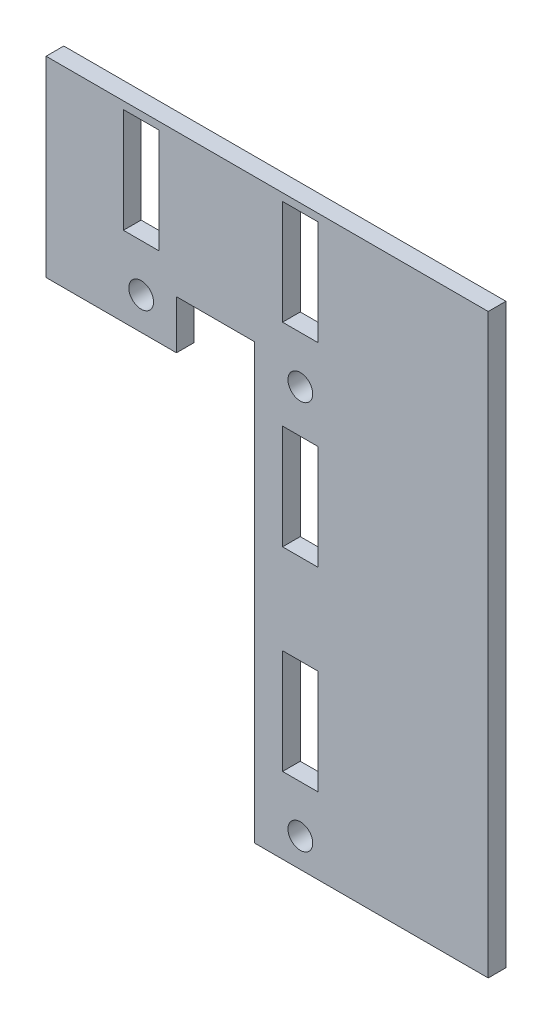
SolidWorks part; units mm, degrees
ref_plane "Front Plane" through (0, 0, 0) normal (1, 0, 0) x (0, 1, 0)
ref_plane "Top Plane" through (0, 0, 0) normal (0, 0, 1) x (0, 1, 0)
ref_plane "Right Plane" through (0, 0, 0) normal (0, 1, 0) x (-1, 0, 0)
sketch "Sketch1" plane through (0, 0, 0) normal (0, 0, 1) x (0, 1, 0)
  line L1 (-50.8, 25.4) -> (50.8, 25.4)
  line L2 (-50.8, 25.4) -> (-50.8, -25.4)
  line L3 (-50.8, -25.4) -> (50.8, -25.4)
  line L4 (50.8, 25.4) -> (50.8, -25.4)
  line L5 (-50.8, 25.4) -> (50.8, -25.4) construction
  line L6 (-50.8, -25.4) -> (50.8, 25.4) construction
  point P0 (0, 0)
  dimension "D1" = 101.6
  dimension "D2" = 50.8
extrude "Boss-Extrude1" add sketch "Sketch1" along normal blind 2.54
sketch "Sketch2" plane through (0, 0, 2.54) normal (0, 0, 1) x (1, 0, 0)
  line L0 (11.1159, -27.94) -> (11.1159, 27.94) construction
  line L1 (11.1159, 27.94) -> (-11.7441, 27.94) construction
  line L2 (-11.7441, 27.94) -> (-11.7441, -27.94) construction
  line L3 (-11.7441, -27.94) -> (11.1159, -27.94) construction
  line L4 (25.4, 50.8) -> (-25.4, 50.8) construction
  circle A0 centre (11.1159, 27.94) radius 1.778
  circle A1 centre (11.1159, -27.94) radius 1.778
  circle A2 centre (-11.7441, 27.94) radius 1.778
  dimension "D3" = 3.556
  dimension "D1" = 55.88
  dimension "D2" = 22.86
  dimension "D4" = 22.86
extrude "Cut-Extrude1" cut sketch "Sketch2" against normal through all
sketch "Sketch3" plane through (0, 0, 2.54) normal (0, 0, 1) x (1, 0, 0)
  line L0 (11.1159, -27.94) -> (11.1159, 27.94) construction
  line L1 (13.6659, -6.16) -> (8.5659, -6.16)
  line L2 (13.6659, -6.16) -> (13.6659, -21.18)
  line L3 (13.6659, -21.18) -> (8.5659, -21.18)
  line L4 (8.5659, -6.16) -> (8.5659, -21.18)
  line L5 (13.6659, -6.16) -> (8.5659, -21.18) construction
  line L6 (13.6659, -21.18) -> (8.5659, -6.16) construction
  line L7 (13.6659, 6.76) -> (8.5659, 6.76)
  line L8 (13.6659, 6.76) -> (13.6659, 21.78)
  line L9 (13.6659, 21.78) -> (8.5659, 21.78)
  line L10 (8.5659, 6.76) -> (8.5659, 21.78)
  line L11 (13.6659, 6.76) -> (8.5659, 21.78) construction
  line L12 (13.6659, 21.78) -> (8.5659, 6.76) construction
  line L13 (13.6659, 34.7) -> (8.5659, 34.7)
  line L14 (13.6659, 34.7) -> (13.6659, 49.72)
  line L15 (13.6659, 49.72) -> (8.5659, 49.72)
  line L16 (8.5659, 34.7) -> (8.5659, 49.72)
  line L17 (13.6659, 34.7) -> (8.5659, 49.72) construction
  line L18 (13.6659, 49.72) -> (8.5659, 34.7) construction
  line L19 (-9.1941, 34.7) -> (-14.2941, 34.7)
  line L20 (-9.1941, 34.7) -> (-9.1941, 49.72)
  line L21 (-9.1941, 49.72) -> (-14.2941, 49.72)
  line L22 (-14.2941, 34.7) -> (-14.2941, 49.72)
  line L23 (-9.1941, 34.7) -> (-14.2941, 49.72) construction
  line L24 (-9.1941, 49.72) -> (-14.2941, 34.7) construction
  circle A0 centre (11.1159, -27.94) radius 1.778 construction
  point P0 (11.1159, -13.67)
  point P10 (11.1159, 14.27)
  point P14 (11.1159, 42.21)
  point P19 (-11.7441, 42.21)
  point P24 (0, 0)
  dimension "D1" = 6.76
  dimension "D3" = 15.02
  dimension "D4" = 27.94
  dimension "D5" = 27.94
  dimension "D6" = 22.86
  dimension "D7" = 5.1
extrude "Cut-Extrude4" cut sketch "Sketch3" against normal through all
sketch "Sketch5" plane through (0, 0, 2.54) normal (0, 0, 1) x (1, 0, 0)
  line L0 (4.5019, -32.102) -> (4.5019, 30.255)
  line L1 (-25.4, -50.8) -> (25.4, -50.8) construction
  line L2 (4.5019, 30.255) -> (-6.6741, 30.255)
  line L3 (-6.6741, 30.255) -> (-6.6741, 23.27)
  line L4 (-6.6741, 23.27) -> (-25.4, 23.27)
  line L5 (-25.4, 50.8) -> (-25.4, -50.8) construction
  line L6 (-25.4, 23.27) -> (-25.4, -50.8)
  line L7 (-25.4, -50.8) -> (25.4, -50.8)
  line L8 (4.5019, -32.102) -> (25.4, -32.102)
  line L9 (25.4, -50.8) -> (25.4, 50.8) construction
  line L10 (25.4, -32.102) -> (25.4, -50.8)
  line L11 (8.5659, -21.18) -> (13.6659, -21.18) construction
  point P17 (0, 0)
  dimension "D1" = 4.064
  dimension "D2" = 4.445
  dimension "D3" = 11.43
  dimension "D4" = 15.24
  dimension "D5" = 10.922
extrude "Cut-Extrude5" cut sketch "Sketch5" against normal through all
sketch "Sketch6" plane through (0, 0, 2.54) normal (0, 0, 1) x (1, 0, 0)
  line L7 (25.4, 50.8) -> (38.1, 50.8)
  line L8 (25.4, 50.8) -> (25.4, -32.102)
  line L9 (25.4, -32.102) -> (38.1, -32.102)
  line L10 (38.1, 50.8) -> (38.1, -32.102)
  line L11 (25.4, 50.8) -> (38.1, -32.102) construction
  line L12 (25.4, -32.102) -> (38.1, 50.8) construction
  line L13 (25.4, -32.102) -> (4.5019, -32.102) construction
  point P10 (31.75, 9.349)
  point P14 (-38.1, 23.27)
  dimension "D2" = 12.7
extrude "Boss-Extrude5" add sketch "Sketch6" along direction (0, 0, 1) on the side against the normal blind 2.54
